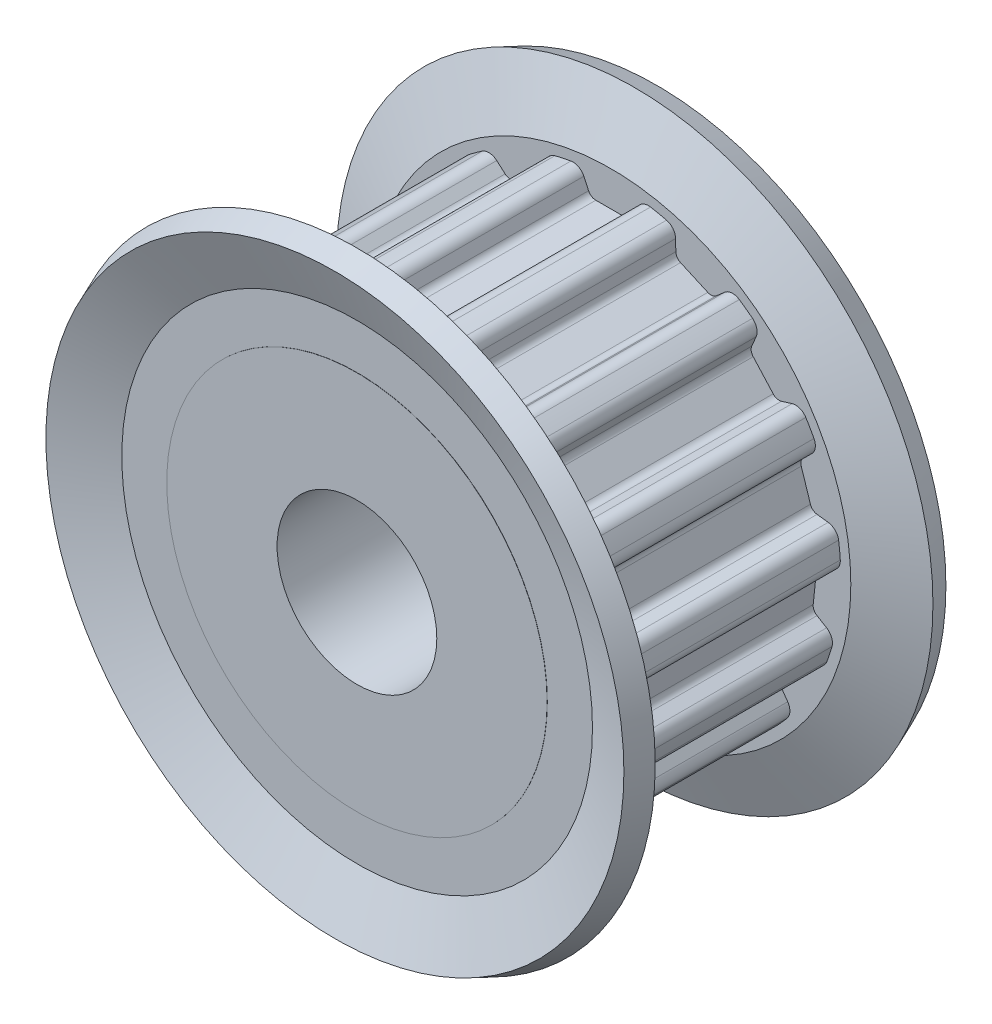
SolidWorks part; units mm, degrees
ref_plane "Front Plane" through (0, 0, 0) normal (0, 0, 1) x (1, 0, 0)
ref_plane "Top Plane" through (0, 0, 0) normal (0, 1, 0) x (1, 0, 0)
ref_plane "Right Plane" through (0, 0, 0) normal (1, 0, 0) x (0, 0, -1)
ref_axis "Axis1" through (0, 0, 55) along (0, 0, -1)
sketch "SketchRevolveGearBelt01" plane through (0, 0, 0) normal (1, 0, 0) x (0, 0, -1)
  line L0 (0, 0) -> (1, 0) construction
  line L1 (6.96, 0) -> (6.96, 9.525)
  line L2 (6.96, 9.525) -> (6.95, 9.525)
  line L3 (6.95, 9.525) -> (6.95, 11.7863)
  line L4 (6.95, 11.7863) -> (8.0633, 14.4741)
  line L5 (8.0633, 14.4741) -> (6.9547, 14.9333)
  line L6 (6.9547, 14.9333) -> (5.75, 12.025)
  line L7 (5.75, 12.025) -> (5.75, 11.525)
  line L8 (5.75, 11.525) -> (-5.75, 11.525)
  line L9 (-5.75, 11.525) -> (-5.75, 12.025)
  line L10 (-5.75, 12.025) -> (-6.9547, 14.9333)
  line L11 (-6.9547, 14.9333) -> (-8.0633, 14.4741)
  line L12 (-8.0633, 14.4741) -> (-6.95, 11.7863)
  line L13 (-6.95, 11.7863) -> (-6.95, 9.525)
  line L14 (-6.95, 9.525) -> (-6.96, 9.525)
  line L15 (-6.96, 9.525) -> (-6.96, 0)
  line L16 (-6.96, 0) -> (6.96, 0)
  dimension "GearBeltSide1" = 6.96
  dimension "GearBeltFlange1OutsideWidth" = 6.95
  dimension "GearBeltFlange1OutsideLength" = 2.2613
  dimension "GearBeltFlange1X" = 1.1133
  dimension "GearBeltFlange1Y" = 2.6878
  dimension "GearBeltFlangeThickness" = 1.2
  dimension "GearBeltToothWidth1" = 5.75
  dimension "GearBeltFlangeInside" = 0.5
  dimension "GearBeltOutsideDiameter" = 11.525
  dimension "GearBeltToothWidth2" = 5.75
  dimension "GearBeltFlange2X" = 1.1133
  dimension "GearBeltFlange2OutsideWidth" = 6.95
revolve "GearBelt01" add sketch "SketchRevolveGearBelt01" angle 360 about L0
sketch "SketchToothGearBelt01" plane through (0, 0, 0) normal (0, 0, 1) x (1, 0, 0)
  line L0 (-1.3466, 11.0138) -> (-1.1098, 10.506)
  line L1 (-0.7473, 10.275) -> (0.7473, 10.275)
  line L2 (1.1098, 10.506) -> (1.3466, 11.0138)
  line L3 (1.9942, 11.3512) -> (0, 13.8912)
  line L4 (0, 13.8912) -> (-1.9942, 11.3512)
  arc A0 (-1.9942, 11.3512) -> (-1.3466, 11.0138) centre (-1.8904, 10.7602) cw
  arc A1 (-1.1098, 10.506) -> (-0.7473, 10.275) centre (-0.7473, 10.675) ccw
  arc A2 (0.7473, 10.275) -> (1.1098, 10.506) centre (0.7473, 10.675) ccw
  arc A3 (1.3466, 11.0138) -> (1.9942, 11.3512) centre (1.8904, 10.7602) cw
  dimension "GearBeltToothR1" = 1.2
  dimension "GearBeltToothR2" = 0.8
  dimension "GearBeltToothX1" = 0.2368
  dimension "GearBeltToothY1" = 0.5078
  dimension "GearBeltToothRootX" = 10.275
  dimension "GearBeltToothRootY" = 10.275
  dimension "GearBeltToothX2" = 0.2368
  dimension "GearBeltToothY2" = 0.5078
  dimension "GearBeltToothCapX1" = 1.9942
  dimension "GearBeltToothCapY1" = 2.54
  dimension "GearBeltToothCapX2" = 1.9942
  dimension "GearBeltToothCapY2" = 2.54
extrude "ToothExtrudeCutGearBelt01" cut sketch "SketchToothGearBelt01" against normal blind 5.75 and the other way blind 5.75
pattern_circular "PatternGearBelt01" count 15 every 24 about axis through (0, 0, 55) along (0, 0, -1) of "ToothExtrudeCutGearBelt01"
sketch "BoreRevolveSketch" plane through (0, 0, 0) normal (1, 0, 0) x (0, 0, -1)
  line L0 (0, 0) -> (1, 0) construction
  line L1 (-6.96, 0) -> (6.96, 0)
  line L2 (6.96, 0) -> (6.96, 4)
  line L3 (6.96, 4) -> (-6.96, 4)
  line L4 (-6.96, 4) -> (-6.96, 0)
  dimension "BoreSide1" = 6.96
  dimension "TaperSide1" = 4
  dimension "BoreSide2" = 6.96
  dimension "TaperSide2" = 4
revolve "BoreRevolveCut" cut sketch "BoreRevolveSketch" angle 360 about L0
sketch "AuxiliarySketchGearBelt01" plane through (0, 0, 0) normal (0, 0, 1) x (1, 0, 0)
  circle A0 centre (0, 0) radius 12.025 construction
  dimension "PitchDiameter" = 24.05
